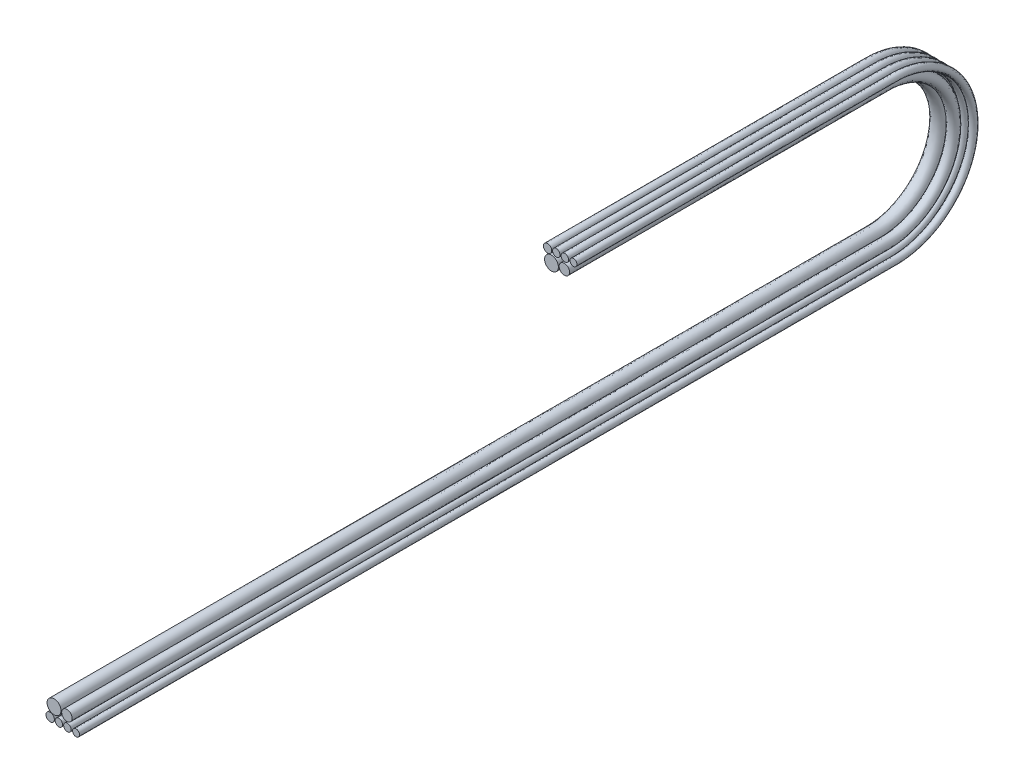
SolidWorks part; units mm, degrees
ref_plane "Front Plane" through (0, 0, 0) normal (0, 0, 1) x (1, 0, 0)
ref_plane "Top Plane" through (0, 0, 0) normal (0, 1, 0) x (1, 0, 0)
ref_plane "Right Plane" through (0, 0, 0) normal (1, 0, 0) x (0, 0, -1)
sketch "Sketch1" plane through (0, 0, 0) normal (0, 0, 1) x (1, 0, 0)
  line L1 (18.5, 18) -> (-18.5, 18) construction
  line L2 (18.5, 18) -> (18.5, 0) construction
  line L3 (18.5, 0) -> (-18.5, 0) construction
  line L4 (-18.5, 18) -> (-18.5, 0) construction
  circle A0 centre (-16.1, 2.4) radius 2.4
  circle A2 centre (-11.0983, 2.15) radius 2.15
  circle A5 centre (-6.1615, 2.15) radius 2.15
  circle A6 centre (-1.1864, 2) radius 2
  circle A7 centre (-13.8535, 8.6823) radius 4
  circle A8 centre (-6.4473, 8.0498) radius 3
  dimension "D3" = 4.8
  dimension "D4" = 4.3
  dimension "D6" = 4
  dimension "D7" = 8
  dimension "D8" = 6
  dimension "D1" = 37
  dimension "D2" = 18
sketch "Sketch2" plane through (0, 0, 0) normal (1, 0, 0) x (0, 0, -1)
  spline S1 degree 3 poles (-999.9965, 9.7) (-509.6383, 9.7) (-19.2081, 9.7) (471.2942, 9.7) (471.5101, 9.7023) (471.6541, 9.7043) (471.7261, 9.7055) (545.1985, 10.9584) (545.1985, 84.4416) (471.7261, 85.6945) (471.6541, 85.6957) (471.5101, 85.6977) (471.2942, 85.7) (76.305, 85.7) (-318.6122, 85.7) (-713.4574, 85.7) knots -1.36443 -1.36443 -1.36443 -1.36443 0.642755 0.64305 0.643345 0.643639 0.643639 0.643639 0.747321 0.747321 0.747321 0.747616 0.747911 0.748205 2.364427 2.364427 2.364427 2.364427 weights 1 1 1 1 1 1 1 0.3447 0.3447 1 1 1 1 1 1 1 only from (0, 9.7) to (286.5369, 85.7) construction
  spline S2 degree 3 poles (0, 9.7) (157.0261, 9.7) (314.1241, 9.7) (471.2942, 9.7) (471.5101, 9.7023) (471.6541, 9.7043) (471.7261, 9.7055) (545.1985, 10.9584) (545.1985, 84.4416) (471.7261, 85.6945) (471.6541, 85.6957) (471.5101, 85.6977) (471.2942, 85.7) (409.6364, 85.7) (348.0506, 85.7) (286.5369, 85.7) knots 0 0 0 0 0.642755 0.64305 0.643345 0.643639 0.643639 0.643639 0.747321 0.747321 0.747321 0.747616 0.747911 0.748205 1 1 1 1 weights 1 1 1 1 1 1 1 0.3447 0.3447 1 1 1 1 1 1 1
sweep "Sweep1" add profiles "Sketch1" path "Sketch2"
